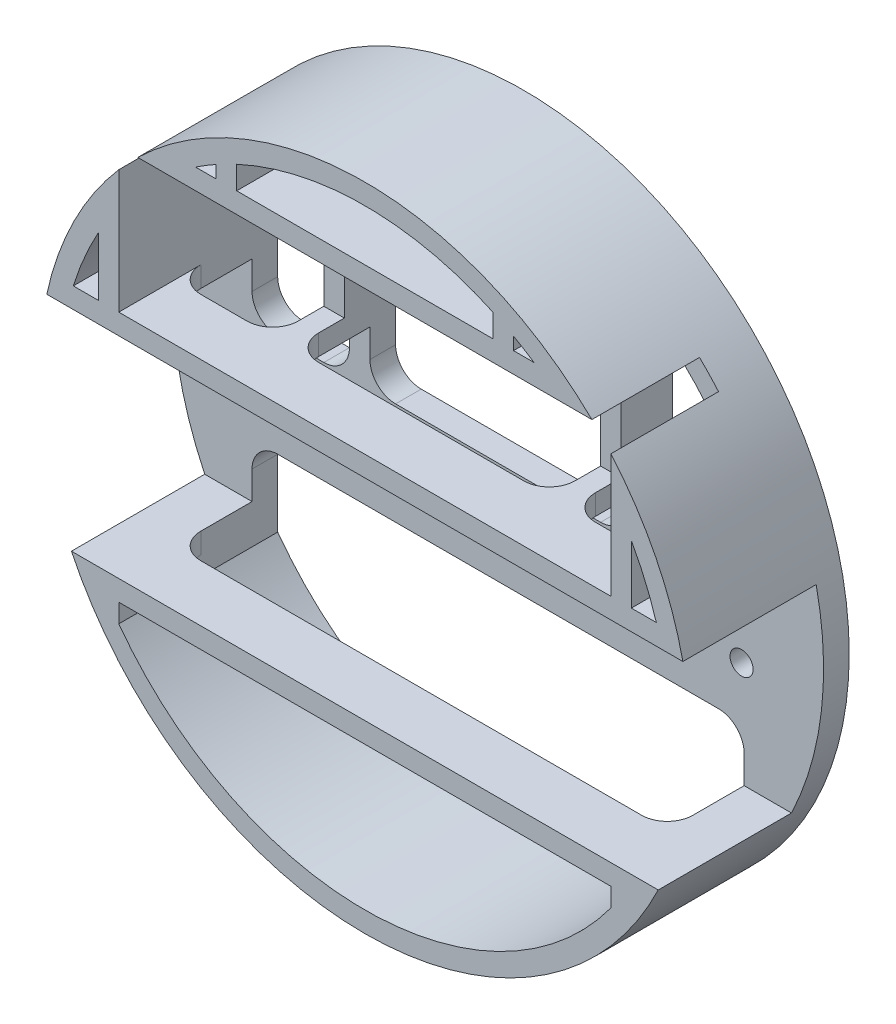
SolidWorks part; units mm, degrees
ref_plane "Front Plane" through (0, 0, 0) normal (0, 0, 1) x (1, 0, 0)
ref_plane "Top Plane" through (0, 0, 0) normal (0, 1, 0) x (1, 0, 0)
ref_plane "Right Plane" through (0, 0, 0) normal (1, 0, 0) x (0, 0, -1)
sketch "Sketch1" plane through (0, 0, 0) normal (0, 0, 1) x (1, 0, 0)
  line L0 (0, -63.5) -> (0, 63.5) construction
  line L1 (-47.5, -7) -> (47.5, -7) construction
  line L2 (-47.5, 7.5) -> (47.5, 7.5)
  line L3 (-47.5, -21.5) -> (47.5, -21.5)
  line L4 (-57.2364, -27.5) -> (57.2364, -27.5)
  line L5 (-48, 17.5) -> (48, 17.5)
  line L6 (-48, 17.5) -> (-48, 45.5)
  line L7 (-48, 45.5) -> (48, 45.5)
  line L8 (48, 17.5) -> (48, 45.5)
  line L9 (-48, 17.5) -> (48, 45.5) construction
  line L10 (-48, 45.5) -> (48, 17.5) construction
  line L11 (-48, 17.5) -> (-56.8683, 17.5)
  line L12 (-52, 17.5) -> (-52, 28.918)
  line L13 (-62.0484, 13.5) -> (62.0484, 13.5)
  line L14 (48, 17.5) -> (56.8683, 17.5)
  line L15 (52, 17.5) -> (52, 28.918)
  line L16 (-33.0151, 49.5) -> (33.0151, 49.5)
  line L17 (-50.4777, -31.5) -> (50.4777, -31.5)
  line L18 (48, 17.5) -> (48, -31.5) construction
  line L19 (48, -31.5) -> (48, -35.1603)
  line L20 (-48, 17.5) -> (-48, -31.5) construction
  line L21 (-48, -31.5) -> (-48, -35.1603)
  circle A0 centre (0, 0) radius 63.5
  arc A2 (-47.5, 7.5) -> (-47.5, -21.5) centre (-47.5, -7) ccw
  arc A3 (47.5, -21.5) -> (47.5, 7.5) centre (47.5, -7) ccw
  circle A4 centre (0, 0) radius 59.5
  point P7 (0, 0)
  point P9 (0, -7)
  point P15 (0, 31.5)
  dimension "D1" = 127
  dimension "D2" = 18
  dimension "D10" = 119
  dimension "D3" = 95
  dimension "D4" = 29
  dimension "D5" = 96
  dimension "D6" = 28
  dimension "D7" = 6
  dimension "D8" = 7
  dimension "D9" = 6
  dimension "D11" = 4
  dimension "D12" = 4
  dimension "D13" = 4
  dimension "D14" = 4
extrude "Boss-Extrude1" add sketch "Sketch1" along normal blind 31 contours A4 L4 A0 | L4 A4 L17 | L13 A4 L14 L5 L11 | L6 A4 L12 L11 | A4 L6 A0 L13 | A4 L13 A0 L8 | L15 A4 L8 L14 | A4 L7 A0 | L7 A4 L16 | L19 A4 L17 | L17 A4 L21
sketch "Sketch2" plane through (0, 0, 0) normal (0, 0, -1) x (-1, 0, 0)
  line L0 (44.2945, 45.5) -> (-44.2945, 45.5) construction
  line L1 (-48, 45.5) -> (-25, 45.5)
  line L2 (-48, 45.5) -> (-48, 17.5)
  line L3 (-48, 17.5) -> (-25, 17.5)
  line L4 (-25, 45.5) -> (-25, 17.5)
  line L5 (48, 17.5) -> (-48, 17.5) construction
  line L6 (48, 17.5) -> (48, 41.5722) construction
  line L7 (25, 45.5) -> (48, 45.5)
  line L8 (25, 45.5) -> (25, 17.5)
  line L9 (25, 17.5) -> (48, 17.5)
  line L10 (48, 45.5) -> (48, 17.5)
  line L11 (-48, 17.5) -> (-48, 41.5722) construction
  arc A0 (48, 41.5722) -> (-48, 41.5722) centre (0, 0) ccw
  line M12 (48, 41.5722) -> (48, 17.5)
  line M13 (48, 17.5) -> (-48, 17.5)
  line M14 (-48, 17.5) -> (-48, 41.5722)
  dimension "D1" = 25
  dimension "D2" = 25
extrude "Boss-Extrude3" add sketch "Sketch2" against normal blind 10 contours A0 L7 L8 M12 M13 | L1 A0 L4 M14 M13
sketch "Sketch4" plane through (0, 0, 0) normal (0, 0, -1) x (-1, 0, 0)
  line L0 (57.2364, -27.5) -> (-57.2364, -27.5) construction
  line L1 (-57.2364, -27.5) -> (57.2364, -27.5)
  line L2 (62.0484, 13.5) -> (-62.0484, 13.5)
  arc A0 (57.2364, -27.5) -> (62.0484, 13.5) centre (0, 0) ccw
  arc A1 (62.0484, 13.5) -> (-62.0484, 13.5) centre (0, 0) ccw construction
  arc A2 (-62.0484, 13.5) -> (-57.2364, -27.5) centre (0, 0) ccw
extrude "Boss-Extrude4" add sketch "Sketch4" against normal blind 5
sketch "Sketch6" plane through (0, 0, 5) normal (0, 0, 1) x (1, 0, 0)
  line L0 (0, 13.5) -> (0, -27.5) construction
  line L1 (-62.0484, 13.5) -> (62.0484, 13.5) construction
  line L2 (57.2364, -27.5) -> (-57.2364, -27.5) construction
  line L3 (-47.5, -7) -> (47.5, -7) construction
  line L4 (-48, 17.5) -> (-48, 13.5) construction
  line L5 (-48, 13.5) -> (-48, 3)
  line L6 (48, 17.5) -> (48, 13.5) construction
  line L7 (-62.0484, 13.5) -> (62.0484, 13.5) construction
  line L8 (48, 13.5) -> (48, 3)
  line L9 (48, 3) -> (-48, 3)
  line L10 (-48, 13.5) -> (48, 13.5)
  line L11 (-48, 3) -> (-48, -17)
  line L12 (-48, -17) -> (48, -17)
  line L13 (48, -17) -> (48, 3)
  line L14 (-48, -17) -> (-48, -27.5)
  line L15 (-57.2364, -27.5) -> (57.2364, -27.5) construction
  line L16 (48, -17) -> (48, -27.5)
  line L17 (-48, -27.5) -> (48, -27.5)
  line L18 (25, 17.5) -> (25, 13.5) construction
  line L19 (-25, 17.5) -> (-25, 13.5) construction
  line L20 (25, 13.5) -> (29, 13.5)
  line L21 (25, 13.5) -> (25, 3)
  line L22 (25, 3) -> (29, 3)
  line L23 (29, 13.5) -> (29, 3)
  line L25 (-25, 13.5) -> (-29, 13.5)
  line L26 (-25, 13.5) -> (-25, 3)
  line L27 (-25, 3) -> (-29, 3)
  line L28 (-29, 13.5) -> (-29, 3)
  circle A0 centre (-47.5, -7) radius 2.25
  circle A1 centre (47.5, -7) radius 2.25
  point P9 (0, -7)
  line M9 (-57.2364, -27.5) -> (57.2364, -27.5)
  line M11 (62.0484, 13.5) -> (-62.0484, 13.5)
  dimension "D1" = 4.5
  dimension "D2" = 4.5
  dimension "D3" = 95
  dimension "D4" = 10
  dimension "D5" = 10
  dimension "D6" = 4
  dimension "D7" = 4
extrude "Cut-Extrude1" cut sketch "Sketch6" against normal through all contours L9 L8 L5 M11 | L16 L12 L14 M9 | L13 A1 | L13 A1 | L11 A0 | L11 A0 | L23 L9 L8 M11 | L28 L5 L9 M11
sketch "Sketch7" plane through (0, 0, 0) normal (0, 0, -1) x (-1, 0, 0)
  line L6 (-29, 17.5) -> (-48, 17.5)
  line L7 (-29, 45.5) -> (-38.3406, 45.5)
  line L8 (-48, 17.5) -> (-48, 35.1603)
  line L9 (-52, 17.5) -> (-52, 28.918) construction
  line L10 (-29, 17.5) -> (-29, 45.5)
  line L11 (-25, 45.5) -> (-25, 17.5) construction
  line L12 (29, 17.5) -> (48, 17.5)
  line L13 (29, 45.5) -> (38.3406, 45.5)
  line L14 (48, 17.5) -> (48, 35.1603)
  line L15 (29, 17.5) -> (29, 45.5)
  line L16 (25, 45.5) -> (25, 17.5) construction
  line L17 (52, 17.5) -> (52, 28.918) construction
  circle A3 centre (0, 0) radius 63.5 construction
  arc A4 (-38.3406, 45.5) -> (-48, 35.1603) centre (0, 0) ccw
  arc A6 (48, 35.1603) -> (38.3406, 45.5) centre (0, 0) ccw
  dimension "D3" = 4
  dimension "D6" = 4
  dimension "D1" = 4
  dimension "D2" = 4
  dimension "D4" = 4
  dimension "D5" = 4
extrude "Cut-Extrude2" cut sketch "Sketch7" against normal blind 10
sketch "Sketch9" plane through (0, 0, 0) normal (0, 0, -1) x (-1, 0, 0)
  line L0 (-48, 13.5) -> (-29, 13.5) construction
  line L1 (-48, -27.5) -> (48, -27.5)
  line L2 (-48, -27.5) -> (-48, -31.5)
  line L3 (-48, -31.5) -> (48, -31.5)
  line L4 (48, -27.5) -> (48, -31.5)
  line L5 (-48, 17.5) -> (-29, 17.5)
  line L6 (-48, 17.5) -> (-48, 13.5)
  line L7 (-48, 13.5) -> (-29, 13.5)
  line L8 (-29, 17.5) -> (-29, 13.5)
  line L9 (25, 45.5) -> (25, 17.5) construction
  line L10 (-25, 17.5) -> (25, 17.5)
  line L11 (-25, 17.5) -> (-25, 13.5)
  line L12 (-25, 13.5) -> (25, 13.5)
  line L13 (25, 17.5) -> (25, 13.5)
  line L14 (29, 17.5) -> (48, 17.5)
  line L15 (29, 17.5) -> (29, 13.5)
  line L16 (29, 13.5) -> (48, 13.5)
  line L17 (48, 17.5) -> (48, 13.5)
  line L18 (-29, 17.5) -> (-29, 45.5) construction
  line L19 (33.0151, 49.5) -> (-33.0151, 49.5) construction
  line L20 (-25, 45.5) -> (25, 45.5)
  line L21 (-25, 45.5) -> (-25, 49.5)
  line L22 (-25, 49.5) -> (25, 49.5)
  line L23 (25, 45.5) -> (25, 49.5)
  line L24 (25, 45.5) -> (25, 17.5) construction
extrude "Cut-Extrude4" cut sketch "Sketch9" against normal blind 20
sketch "Sketch10" plane through (0, 0, 0) normal (0, 0, -1) x (-1, 0, 0)
  line L0 (-29.0076, 49.5) -> (-29.0076, 51.9501)
  line L1 (-25, 49.5) -> (-33.0151, 49.5) construction
  line L2 (-25, 49.5) -> (-25, 53.9931)
  line L3 (-29.0076, 49.5) -> (-25, 49.5)
  line L4 (25, 49.5) -> (25, 53.9931)
  line L5 (29.0076, 49.5) -> (29.0076, 51.9501)
  line L6 (33.0151, 49.5) -> (25, 49.5) construction
  line L7 (29.0076, 49.5) -> (25, 49.5)
  arc A0 (33.0151, 49.5) -> (-33.0151, 49.5) centre (0, 0) ccw construction
  arc A1 (-29.0076, 51.9501) -> (-25, 53.9931) centre (0, 0) cw
  arc A2 (29.0076, 51.9501) -> (25, 53.9931) centre (0, 0) ccw
  line M21 (-25, 49.5) -> (-33.0151, 49.5)
  arc M22 (-33.0151, 49.5) -> (33.0151, 49.5) centre (0, 0) cw
  line M23 (33.0151, 49.5) -> (25, 49.5)
extrude "Boss-Extrude5" add sketch "Sketch10" against normal up to surface (31 mm away) contours L2 L0 M21 M22 | L5 L4 M23 M22
fillet "Fillet3" radius 5 18 edges at (25, 47.5, 20) (48, 15.5, 20) (-29, 15.5, 20) (25, 15.5, 20) (-29, 3, 2.5) (25, 3, 2.5) (48, 3, 2.5) (48, -29.5, 20) (48, -17, 2.5) (-48, -17, 2.5) (-48, -29.5, 20) (29, 3, 2.5) (-25, 3, 2.5) (-48, 3, 2.5) (-25, 47.5, 20) (-48, 15.5, 20) (-25, 15.5, 20) (29, 15.5, 20)
